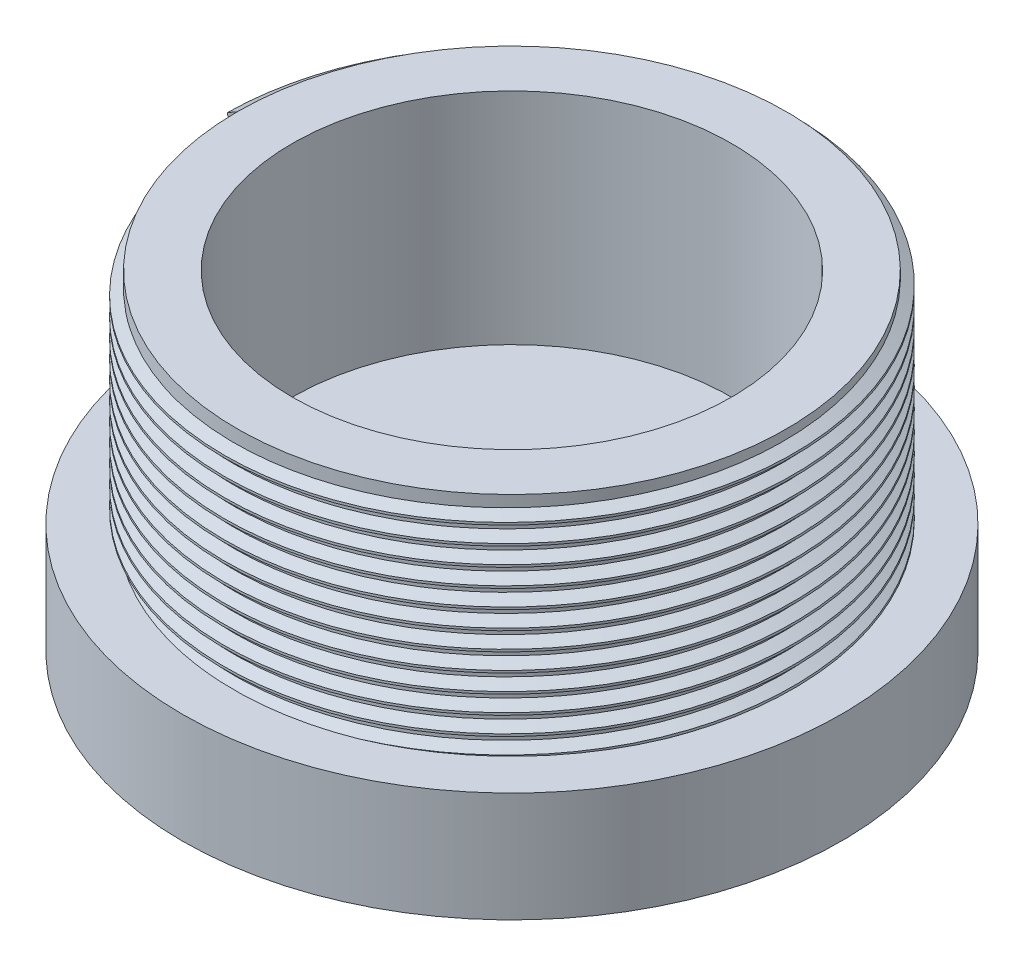
SolidWorks part; units mm, degrees
ref_plane "Front Plane" through (0, 0, 0) normal (0, 0, 1) x (1, 0, 0)
ref_plane "Top Plane" through (0, 0, 0) normal (0, 1, 0) x (1, 0, 0)
ref_plane "Right Plane" through (0, 0, 0) normal (1, 0, 0) x (0, 0, -1)
sketch "Sketch1" plane through (0, 0, 0) normal (0, 1, 0) x (1, 0, 0)
  circle A0 centre (0, 0) radius 38.1
  dimension "D1" = 76.2
extrude "Boss-Extrude1" add sketch "Sketch1" along normal blind 12.7
sketch "Sketch2" plane through (0, 12.7, 0) normal (0, 1, 0) x (1, 0, 0)
  circle A0 centre (0, 0) radius 31.75
  dimension "D1" = 63.5
extrude "Boss-Extrude2" add sketch "Sketch2" along normal blind 25.4
thread "Thread1" pitch 2.1167 method extrude profile "Thread Profile1" start angle 0, offset 0, length 25.24, pitch 2.1167, diameter 63.5
ref_plane "Plane1" through (-31.75, 38.1, 0) normal (0, 0, 1) x (-1, 0, 0)
sketch "Thread Profile1" plane through (-31.75, 38.1, 0) normal (0, 0, 1) x (-1, 0, 0)
  line L0 (0, 0) -> (0, 2.1167) construction
  line L1 (0, 0) -> (1.1457, 0.6615)
  line L2 (1.1457, 0.6615) -> (1.1457, 0.926)
  line L3 (1.1457, 0.926) -> (0, 1.5875)
  line L4 (1.1457, 0.7937) -> (0, 0.7937) construction
  line L11 (0, 0) -> (0, 1.5875)
  point P2 (0, 0)
  dimension "Pitch" = 2.1167
  dimension "Profile_Angle" = 60
  dimension "Profile_Land" = 0.2646
  dimension "Profile_Height" = 1.1457
sketch "Sketch7" plane through (0, 38.1, 0) normal (0, 1, 0) x (1, 0, 0)
  circle A0 centre (0, 0) radius 25.4
  dimension "D1" = 50.8
extrude "Cut-Extrude1" cut sketch "Sketch7" against normal blind 25.4
